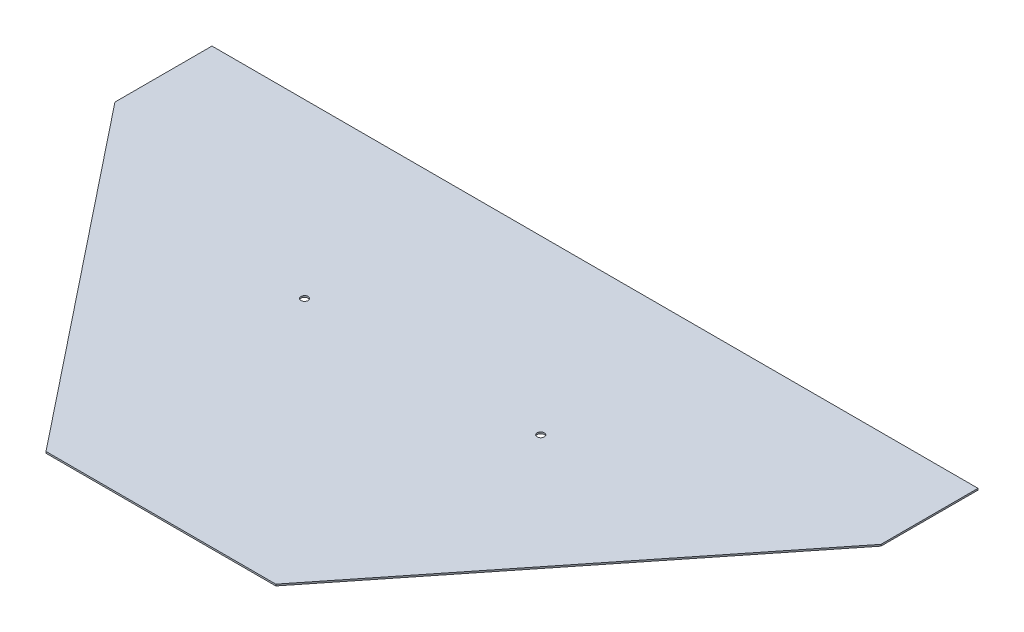
SolidWorks part; units mm, degrees
ref_plane "Front Plane" through (0, 0, 0) normal (0, 0, 1) x (1, 0, 0)
ref_plane "Top Plane" through (0, 0, 0) normal (0, 1, 0) x (1, 0, 0)
ref_plane "Right Plane" through (0, 0, 0) normal (1, 0, 0) x (0, 0, -1)
sketch "Sketch1" plane through (0, 0, 0) normal (0, 1, 0) x (1, 0, 0)
  line L0 (0, 0) -> (457.2, 0)
  line L1 (457.2, 0) -> (990.6, 670.56)
  line L2 (990.6, 670.56) -> (990.6, 863.6)
  line L3 (990.6, 863.6) -> (-533.4, 863.6)
  line L4 (-533.4, 863.6) -> (-533.4, 670.56)
  line L5 (-533.4, 670.56) -> (0, 0)
  line L6 (228.6, 863.6) -> (228.6, 0) construction
  dimension "D1" = 457.2
  dimension "D2" = 863.6
  dimension "D3" = 193.04
  dimension "D4" = 1524
extrude "Boss-Extrude1" add sketch "Sketch1" along normal blind 3.175
sketch "Sketch2" plane through (0, 3.175, 0) normal (0, 1, 0) x (1, 0, 0)
  line L0 (-6.35, 520.7) -> (463.55, 520.7) construction
  line L1 (228.6, 520.7) -> (228.6, 0) construction
  line L2 (0, 0) -> (457.2, 0) construction
  line L3 (990.6, 863.6) -> (-533.4, 863.6) construction
  circle A0 centre (-6.35, 520.7) radius 7.1437
  circle A1 centre (463.55, 520.7) radius 7.1438
  dimension "D2" = 14.2875
  dimension "D1" = 469.9
  dimension "D3" = 342.9
extrude "Cut-Extrude1" cut sketch "Sketch2" against normal up to next
